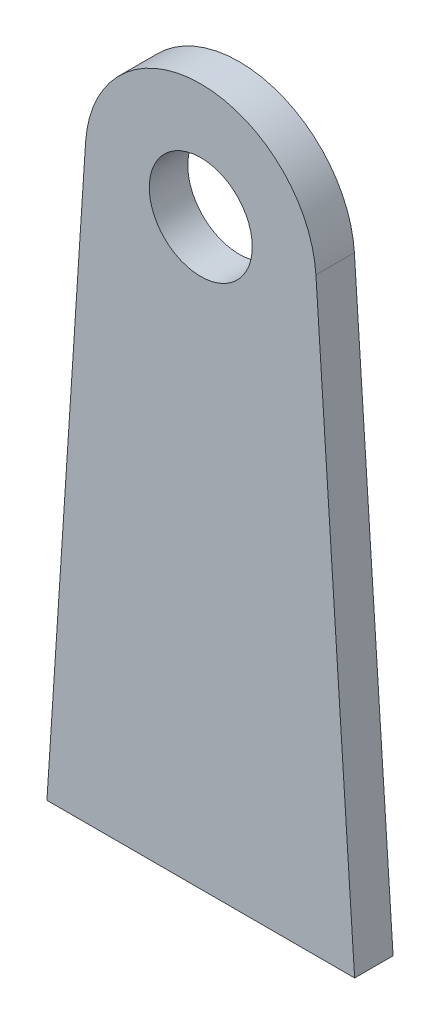
SolidWorks part; units mm, degrees
ref_plane "Front Plane" through (0, 0, 0) normal (0, 0, 1) x (1, 0, 0)
ref_plane "Top Plane" through (0, 0, 0) normal (0, 1, 0) x (1, 0, 0)
ref_plane "Right Plane" through (0, 0, 0) normal (1, 0, 0) x (0, 0, -1)
sketch "Sketch1" plane through (0, 0, 0) normal (0, 0, 1) x (1, 0, 0)
  line L0 (0, 0) -> (0, -48.0437)
  line L1 (-12.7, -48.0437) -> (12.7, -48.0437)
  line L2 (12.7, -48.0437) -> (9.5045, 0.6241)
  line L3 (-12.7, -48.0437) -> (-9.5045, 0.6241)
  circle A0 centre (0, 0) radius 4.25
  circle A1 centre (0, 0) radius 9.525
  dimension "D2" = 8.5
  dimension "D3" = 19.05
  dimension "D1" = 12.7
sketch "Sketch2" [suppressed] plane through (0, 0, 0) normal (0, 0, 1) x (1, 0, 0)
  line L0 (-5.6668, 0) -> (-5.6668, -47.8557)
  line L1 (-18.3668, -47.8557) -> (7.0332, -47.8557)
  line L2 (7.0332, -47.8557) -> (3.8376, 0.6265)
  line L3 (-18.3668, -47.8557) -> (-15.1712, 0.6265)
  circle A0 centre (-5.6668, 0) radius 4.25
  circle A1 centre (-5.6668, 0) radius 9.525
  dimension "D2" = 8.5
  dimension "D3" = 19.05
  dimension "D1" = 12.7
extrude "Boss-Extrude1" add sketch "Sketch1" along normal blind 3.175 contours A1 A0 | A1 L3 L1 L0 | A1 L0 L1 L2 region at (-6.7557, -6.3267, 0) region at (5.8381, -28.4057, 0) region at (-5.8381, -28.4057, 0)
extrude "Boss-Extrude2" [suppressed] add sketch "Sketch2" along normal blind 3.175 contours A1 A0 | A1 L3 L1 L0 | A1 L0 L1 L2
